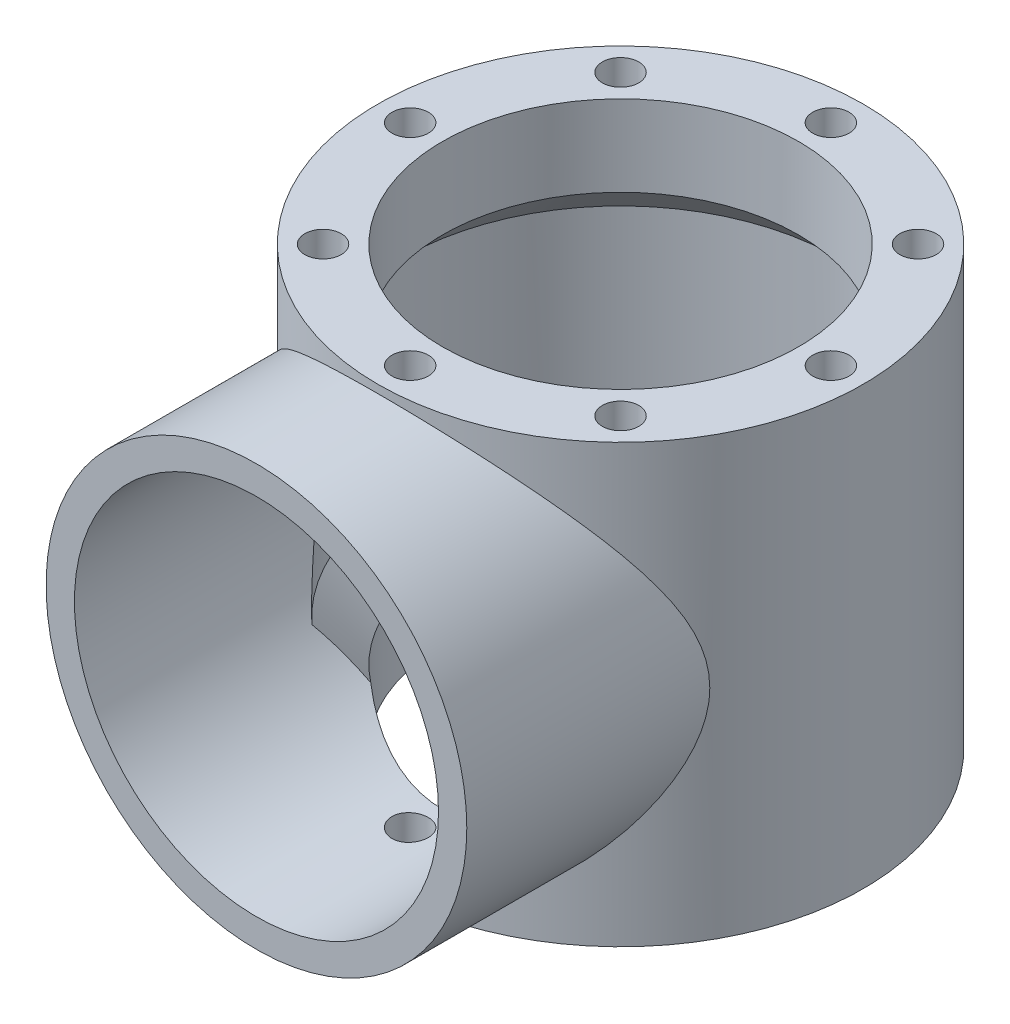
SolidWorks part; units mm, degrees
ref_plane "Спереди" through (0, 0, 0) normal (0, 0, 1) x (1, 0, 0)
ref_plane "Сверху" through (0, 0, 0) normal (0, 1, 0) x (1, 0, 0)
ref_plane "Справа" through (0, 0, 0) normal (1, 0, 0) x (0, 0, -1)
sketch "Эскиз1" plane through (0, 0, 0) normal (0, 1, 0) x (1, 0, 0)
  circle A0 centre (0, 0) radius 22
  circle A1 centre (0, 0) radius 30
  dimension "D1" = 44
  dimension "D2" = 60
extrude "Бобышка-Вытянуть1" add sketch "Эскиз1" along normal blind 54
sketch "Эскиз3" plane through (0, 54, 0) normal (0, 1, 0) x (1, 0, 0)
  line L0 (0, 30) -> (0, -30) construction
  circle A0 centre (0, 0) radius 26 construction
  circle A1 centre (0, 0) radius 30 construction
  circle A2 centre (0, 26) radius 2
  circle A3 centre (18.3848, 18.3848) radius 2
  circle A4 centre (26, 0) radius 2
  circle A5 centre (18.3848, -18.3848) radius 2
  circle A6 centre (0, -26) radius 2
  circle A7 centre (-18.3848, -18.3848) radius 2
  circle A8 centre (-26, 0) radius 2
  circle A9 centre (-18.3848, 18.3848) radius 2
  point P26 (0, 0)
  dimension "D1" = 8
hole_wizard "Отверстие с зазором M41" positions "Эскиз4" profile "Эскиз5" hole size "M4" standard "ISO"
sketch "Эскиз4" plane through (0, 54, 0) normal (0, 1, 0) x (1, 0, 0)
  point P0 (-18.3848, 18.3848)
  point P3 (0, 26)
  point P6 (18.3848, 18.3848)
  point P9 (26, 0)
  point P12 (18.3848, -18.3848)
  point P15 (0, -26)
  point P18 (-18.3848, -18.3848)
  point P21 (-26, 0)
sketch "Эскиз5" plane through (-18.3848, 54, -18.3848) normal (1, 0, 0) x (0, 0, 1)
  line L0 (0, 0) -> (0, 9.3519)
  line L1 (0, 9.3519) -> (2.25, 8)
  line L2 (2.25, 8) -> (2.25, 0)
  line L5 (2.25, 0) -> (0, 0)
  line L10 (0, 9.3519) -> (-2.25, 8) construction
  line L11 (0, -6.35) -> (0, 107.95) construction
  dimension "Диаметр отверстия" = 4.5
  dimension "Глубина отверстия" = 8
  dimension "Угол заточки сверла" = 118
ref_plane "Плоскость1" through (0, 27, 0) normal (0, 1, 0) x (1, 0, 0)
mirror "Зеркальное отражение1" about plane through (0, 27, 0) normal (0, 1, 0) of "Отверстие с зазором M41"
ref_plane "Плоскость2" through (0, 0, 0) normal (0, 0, 1) x (1, 0, 0)
ref_plane "Плоскость3" through (0, 0, 45) normal (0, 0, 1) x (1, 0, 0)
sketch "Эскиз6" plane through (0, 0, 45) normal (0, 0, 1) x (1, 0, 0)
  line L0 (0, 0) -> (0, 54) construction
  line L1 (0, 27) -> (39.3345, 27) construction
  line L2 (33, 27) -> (-33, 27) construction
  line L3 (39.3345, 27) -> (-33.9059, 27) construction
  circle A0 centre (0, 27) radius 20
sketch "Эскиз7" plane through (0, 0, 45) normal (0, 0, 1) x (1, 0, 0)
  line L0 (0, 0) -> (0, 54) construction
  line L1 (0, 54) -> (0, 27) construction
  line L2 (0, 27) -> (-37.0029, 27) construction
  line L3 (-37.0029, 27) -> (37.9953, 27) construction
  circle A0 centre (0, 27) radius 22.5
  circle A1 centre (0, 27) radius 26
  dimension "D1" = 52
  dimension "D2" = 45
extrude "Бобышка-Вытянуть2" add sketch "Эскиз7" against normal up to next
sketch "Эскиз8" plane through (0, 0, 0) normal (0, -1, 0) x (1, 0, 0)
  circle A1 centre (0, 0) radius 27
  dimension "D2" = 54
extrude "Вырез-Вытянуть1" cut sketch "Эскиз8" against normal blind 25 from offset 14 offset against normal yes
chamfer "Фаска2" distance 5 angle 45 2 edges at (0, 39, -22) (0, 14, -22)
sketch "Эскиз9" plane through (0, 0, 45) normal (0, 0, 1) x (1, 0, 0)
  circle A0 centre (0, 27) radius 22.5
  dimension "D1" = 45
  dimension "D2" = 27
extrude "Вырез-Вытянуть2" cut sketch "Эскиз9" against normal up to vertex (45 mm away) up to point (0, 0, 0)
